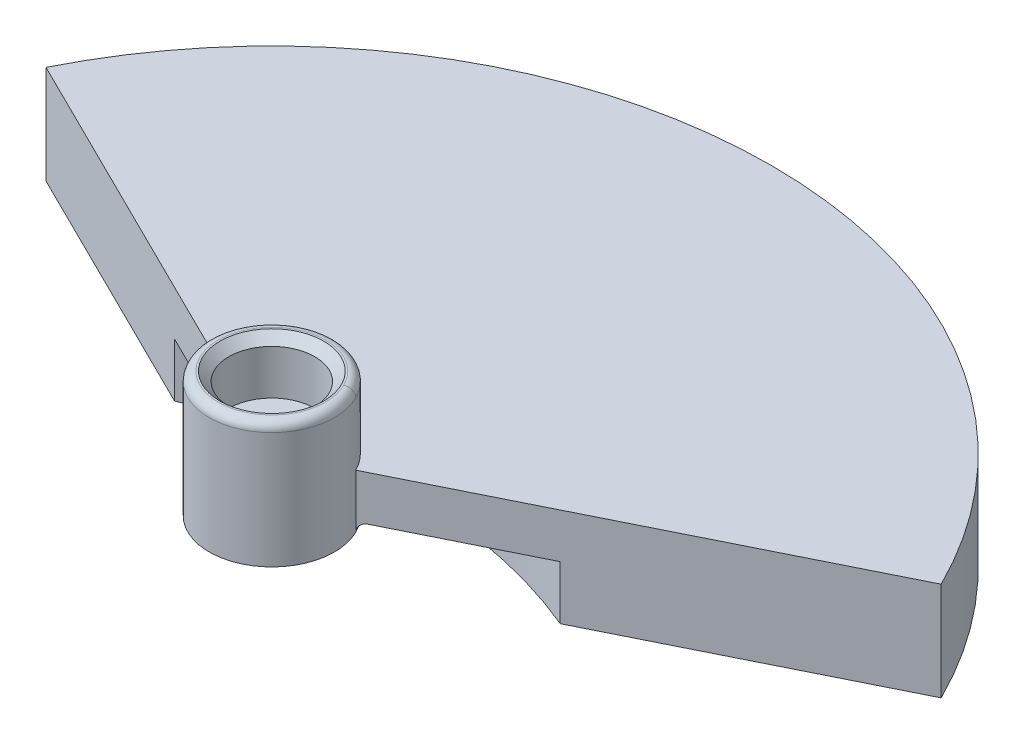
SolidWorks part; units mm, degrees
ref_plane "Front Plane" through (0, 0, 0) normal (0, 0, 1) x (1, 0, 0)
ref_plane "Top Plane" through (0, 0, 0) normal (0, 1, 0) x (1, 0, 0)
ref_plane "Right Plane" through (0, 0, 0) normal (1, 0, 0) x (0, 0, -1)
sketch "Sketch1" plane through (0, 0, 0) normal (0, 1, 0) x (1, 0, 0)
  circle A0 centre (0, 0) radius 2.5
  circle A1 centre (0, 0) radius 3.5
  dimension "D1" = 5
  dimension "D2" = 1
extrude "Boss-Extrude1" add sketch "Sketch1" along normal blind 3
sketch "Sketch2" plane through (0, 3, 0) normal (0, 1, 0) x (1, 0, 0)
  circle A0 centre (0, 0) radius 3.5
extrude "Boss-Extrude2" add sketch "Sketch2" along normal blind 1
sketch "Sketch3" plane through (0, 4, 0) normal (0, 1, 0) x (1, 0, 0)
  circle A0 centre (0, 0) radius 1.3
  dimension "D1" = 2.6
extrude "Cut-Extrude1" cut sketch "Sketch3" against normal up to next
sketch "Sketch4" plane through (0, 4, 0) normal (0, 1, 0) x (1, 0, 0)
  circle A0 centre (0, 0) radius 2.4
  circle A1 centre (0, 0) radius 3.5
  dimension "D1" = 4.8
extrude "Boss-Extrude3" add sketch "Sketch4" along normal blind 3
chamfer "Chamfer1" distance 0.5 angle 45 2 edges at (0, 7, 2.4) (0, 0, 2.5)
ref_plane "Plane1" through (0, 3.5, 0) normal (0, 1, 0) x (1, 0, 0)
sketch "Sketch5" plane through (0, 3.5, 0) normal (0, 1, 0) x (1, 0, 0)
  line L0 (0, 0) -> (15.4603, 0) construction
  arc A0 (-0.0885, -3.4989) -> (21.9115, -1) centre (1.9409, 76.7271) ccw
  circle A1 centre (0, 0) radius 3.5 construction
  arc A3 (-0.0885, 3.4989) -> (21.9115, 1) centre (1.9409, -76.7271) cw
  arc A4 (21.9115, 1) -> (21.9115, -1) centre (21.6546, 0) cw
  arc A5 (-0.0885, -3.4989) -> (-0.0885, 3.4989) centre (0, 0) ccw
  dimension "D1" = 22
  dimension "D2" = 1
extrude "Boss-Extrude4" [suppressed] add sketch "Sketch5" along normal blind 1 and the other way blind 1
sketch "Sketch6" plane through (0, 3.5, 0) normal (0, 1, 0) x (1, 0, 0)
  line L0 (-25, 12.3859) -> (-3.1362, 1.5538)
  line L1 (25, 12.3859) -> (3.1362, 1.5538)
  line L2 (0, 0) -> (0, -4.7859) construction
  arc A0 (-25, 12.3859) -> (25, 12.3859) centre (0, 0) cw
  circle A1 centre (0, 0) radius 2.9 construction
  circle A2 centre (0, 0) radius 3.5 construction
  arc A3 (-3.1362, 1.5538) -> (3.1362, 1.5538) centre (0, 0) cw
  dimension "D1" = 25
extrude "Boss-Extrude5" add sketch "Sketch6" along normal up to surface (3.5 mm away) and the other way offset from surface 0.5 up to face at (0, 7, 2.9) other way up to face at (0, 0, 3)
fillet "Fillet1" radius 0.5 2 edges at (0, 7, 3.5) (0, 0.5, -3.5)
sketch "Sketch7" plane through (0, 0.5, 0) normal (0, -1, 0) x (1, 0, 0)
  line L0 (-3.5842, -1.7758) -> (-25, -12.3859) construction
  line L1 (25, -12.3859) -> (3.5842, -1.7758) construction
  line L4 (25, -12.3859) -> (3.5842, -1.7758)
  line L5 (-3.5842, -1.7758) -> (-25, -12.3859)
  line L6 (25, -12.3859) -> (10.7718, -5.3367)
  line L7 (-10.7718, -5.3367) -> (-25, -12.3859)
  arc A0 (-10.7718, -5.3367) -> (10.7718, -5.3367) centre (0, 20.4) ccw
  arc A2 (-3.1362, -1.5538) -> (3.1362, -1.5538) centre (0, 0) ccw construction
  arc A3 (-25, -12.3859) -> (25, -12.3859) centre (0, 0) ccw construction
  arc A6 (-3.5842, -1.7758) -> (3.5842, -1.7758) centre (0, 0) ccw
  arc A7 (-25, -12.3859) -> (25, -12.3859) centre (0, 0) ccw
  arc A9 (-25, -12.3859) -> (25, -12.3859) centre (0, 0) ccw
  point P10 (0, -7.5)
  dimension "D1" = 4
  dimension "D2" = 0
extrude "Boss-Extrude6" add sketch "Sketch7" along normal blind 3
sketch "Sketch8" plane through (0, 7, 0) normal (0, 1, 0) x (1, 0, 0)
  line L2 (2.6882, 1.3318) -> (25, 12.3859)
  line L3 (-25, 12.3859) -> (-2.6882, 1.3318)
  line L4 (3.1362, 1.5538) -> (25, 12.3859)
  line L5 (-25, 12.3859) -> (-3.1362, 1.5538)
  arc A1 (-3.1362, 1.5538) -> (3.1362, 1.5538) centre (0, 0) cw
  arc A2 (-2.6882, 1.3318) -> (2.6882, 1.3318) centre (0, 0) ccw
  arc A3 (25, 12.3859) -> (-25, 12.3859) centre (0, 0) ccw
  arc A5 (25, 12.3859) -> (-25, 12.3859) centre (0, 0) ccw
  arc A6 (-3.1362, 1.5538) -> (3.1362, 1.5538) centre (0, 0) ccw construction
  dimension "D1" = 0
extrude "Cut-Extrude2" cut sketch "Sketch8" against normal blind 4
fillet "Fillet3" radius 0.5 1 edges at (0, 7, -3.5)
